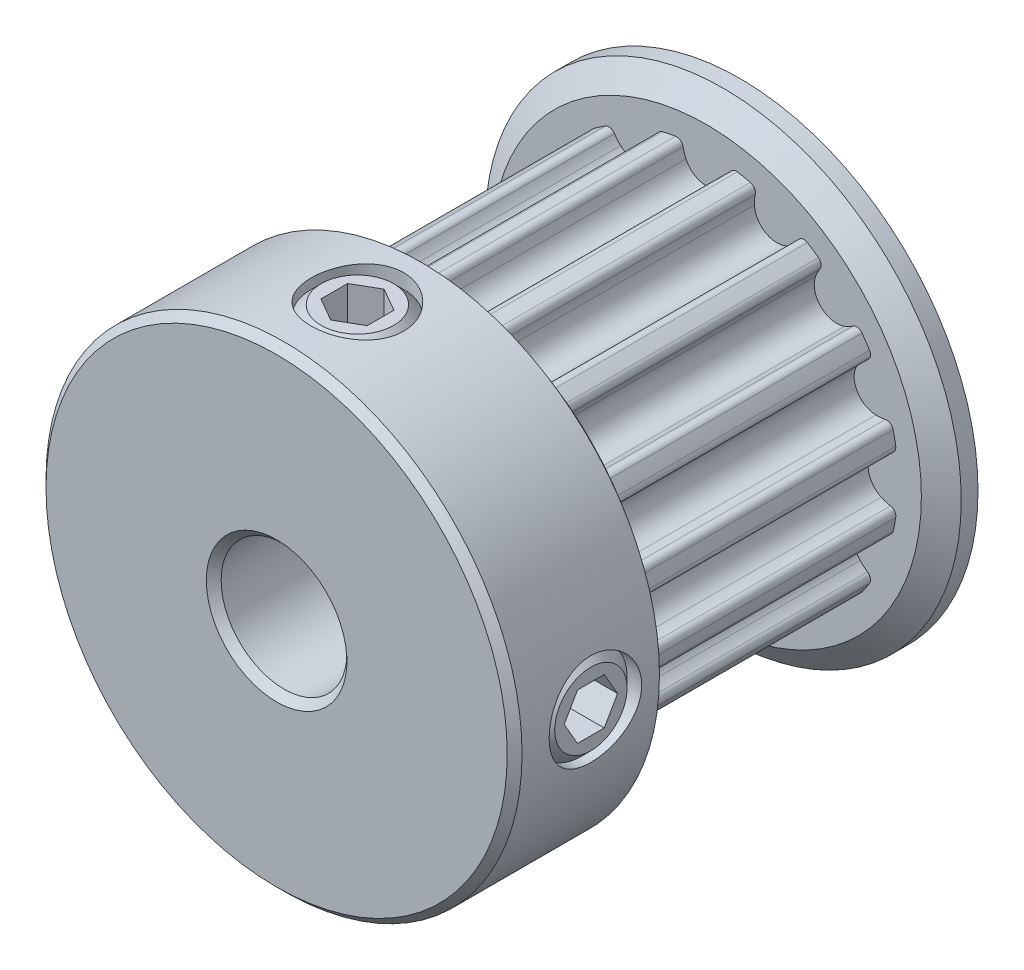
SolidWorks part; units mm, degrees
ref_plane "Front Plane" through (0, 0, 0) normal (0, 0, 1) x (1, 0, 0)
ref_plane "Top Plane" through (0, 0, 0) normal (0, 1, 0) x (1, 0, 0)
ref_plane "Right Plane" through (0, 0, 0) normal (1, 0, 0) x (0, 0, -1)
sketch "Sketch1" plane through (0, 0, 0) normal (0, 0, 1) x (1, 0, 0)
  line L1 (-2.553, 6.1245) -> (2.553, 6.1245) construction
  line L4 (0, 0) -> (0, 6.1245) construction
  line L5 (0, 6.1245) -> (0, 12.0665) construction
  line L6 (0, 7.6455) -> (2.9417, 7.0569) construction
  line L7 (2.9417, 7.0569) -> (3.8741, 6.6682) construction
  line L8 (2.9417, 7.0569) -> (2.553, 6.1245) construction
  line L9 (-2.9417, 7.0569) -> (-2.553, 6.1245) construction
  line L10 (-2.7951, 6.7052) -> (-3.7579, 9.015)
  line L11 (-3.7579, 9.015) -> (3.7579, 9.015)
  line L12 (3.7579, 9.015) -> (2.7951, 6.7052)
  circle A0 centre (0, 0) radius 7.6455 construction
  circle A1 centre (0, 0) radius 9.015 construction
  circle A2 centre (0, 0) radius 7.2645 construction
  arc A3 (-0.7739, 6.6229) -> (0.7739, 6.6229) centre (0, 6.9745) ccw
  arc A4 (-0.7739, 6.6229) -> (-0.8836, 6.9694) centre (0.61, 7.2516) cw
  arc A5 (-2.7951, 6.7052) -> (-1.1695, 7.1697) centre (0, 0) cw
  arc A6 (-0.8836, 6.9694) -> (-1.1695, 7.1697) centre (-1.1292, 6.923) ccw
  arc A7 (2.7951, 6.7052) -> (1.1695, 7.1697) centre (0, 0) ccw
  arc A8 (0.8836, 6.9694) -> (1.1695, 7.1697) centre (1.1292, 6.923) cw
  arc A9 (0.7739, 6.6229) -> (0.8836, 6.9694) centre (-0.61, 7.2516) ccw
  point P6 (0, 20.9083)
  point P11 (0, 7.6455)
  point P13 (0, 9.015)
  point P14 (0, 7.2645)
  dimension "D1" = 8.8419
  dimension "D2" = 4.421
sketch "Sketch2" plane through (0, 0, 0) normal (1, 0, 0) x (0, 0, -1)
  line L0 (-8.775, 2.3812) -> (8.775, 2.3812)
  line L1 (-8.775, 2.3812) -> (-8.775, 9.015)
  line L2 (-3.29, 9.015) -> (-8.775, 9.015)
  line L3 (-3.925, 2.3813) -> (-3.925, 9.015) construction
  line L4 (-3.925, 9.015) -> (-2.655, 9.015) construction
  line L5 (-2.655, 9.015) -> (-2.655, 7.2645) construction
  line L6 (-2.655, 7.2645) -> (7.505, 7.2645)
  line L7 (7.505, 7.2645) -> (7.505, 9.015) construction
  line L8 (7.505, 9.015) -> (8.775, 9.015) construction
  line L9 (8.775, 9.015) -> (8.775, 2.3812)
  line L10 (-8.775, 0) -> (8.775, 0) construction
  line L11 (8.14, 9.015) -> (7.505, 8.1398)
  line L12 (-2.655, 8.1398) -> (-3.29, 9.015)
  line L14 (-2.655, 8.1398) -> (-2.655, 7.2645)
  line L15 (7.505, 7.2645) -> (7.505, 8.1398)
  line L16 (8.14, 9.015) -> (8.775, 9.015)
  arc A0 (-2.655, 8.1398) -> (-3.29, 9.015) centre (-3.5757, 8.1398) ccw construction
  arc A1 (7.505, 8.1398) -> (8.14, 9.015) centre (8.4257, 8.1398) cw construction
  point P12 (-2.655, 8.1398)
  point P14 (-3.29, 9.015)
  point P20 (7.505, 8.1398)
  point P21 (8.14, 9.015)
  point P25 (7.505, 0)
  point P26 (-2.655, 0)
  dimension "OA" = 17.55
  dimension "Bore" = 4.7625
  dimension "Outside Width" = 11.43
  dimension "Inside Width" = 10.16
revolve "Revolve1" add sketch "Sketch2" angle 360 mid plane about L10
sketch "Sketch3" plane through (0, 0, 0) normal (0, 0, 1) x (1, 0, 0)
  line L6 (3.7579, 9.015) -> (-3.7579, 9.015)
  line L7 (2.7951, 6.7052) -> (3.7579, 9.015)
  line L8 (-3.7579, 9.015) -> (-2.7951, 6.7052)
  line L9 (3.7579, 9.015) -> (-3.7579, 9.015)
  line L10 (2.7951, 6.7052) -> (3.7579, 9.015)
  line L11 (-3.7579, 9.015) -> (-2.7951, 6.7052)
  arc A8 (2.7951, 6.7052) -> (1.1695, 7.1697) centre (0, 0) ccw
  arc A9 (1.1695, 7.1697) -> (0.8836, 6.9694) centre (1.1292, 6.923) ccw
  arc A10 (0.7739, 6.6229) -> (0.8836, 6.9694) centre (-0.61, 7.2516) ccw
  arc A11 (-0.7739, 6.6229) -> (0.7739, 6.6229) centre (0, 6.9745) ccw
  arc A12 (-0.8836, 6.9694) -> (-0.7739, 6.6229) centre (0.61, 7.2516) ccw
  arc A13 (-0.8836, 6.9694) -> (-1.1695, 7.1697) centre (-1.1292, 6.923) ccw
  arc A14 (-1.1695, 7.1697) -> (-2.7951, 6.7052) centre (0, 0) ccw
  arc A15 (2.7951, 6.7052) -> (1.1695, 7.1697) centre (0, 0) ccw
  arc A16 (1.1695, 7.1697) -> (0.8836, 6.9694) centre (1.1292, 6.923) ccw
  arc A17 (0.7739, 6.6229) -> (0.8836, 6.9694) centre (-0.61, 7.2516) ccw
  arc A18 (-0.7739, 6.6229) -> (0.7739, 6.6229) centre (0, 6.9745) ccw
  arc A19 (-0.8836, 6.9694) -> (-0.7739, 6.6229) centre (0.61, 7.2516) ccw
  arc A20 (-0.8836, 6.9694) -> (-1.1695, 7.1697) centre (-1.1292, 6.923) ccw
  arc A21 (-1.1695, 7.1697) -> (-2.7951, 6.7052) centre (0, 0) ccw
  dimension "D1" = 0
extrude "Cut-Extrude1" cut sketch "Sketch3" against normal up to vertex (7.505 mm away) from vertex up to point (0, 7.2645, -7.505) starting at point (0, 7.2645, 2.655)
pattern_circular "CirPattern1" count 16 over 360 about axis through (0, 0, 8.775) along (0, 0, 1) of "Cut-Extrude1"
sketch "Sketch4" plane through (0, 0, 0) normal (1, 0, 0) x (0, -1, 0)
  line L0 (0, -2.655) -> (0, -8.775) construction
  line L1 (-2.3812, -8.775) -> (2.3812, -8.775) construction
  line L2 (8.1398, -2.655) -> (-8.1398, -2.655) construction
  circle A0 centre (0, -5.715) radius 1.7526
extrude "Cut-Extrude2" cut sketch "Sketch4" along normal through all
ref_plane "Plane1" through (0, 0, 5.715) normal (0, 0, 1) x (1, 0, 0)
sketch "Sketch5" plane through (0, 0, 5.715) normal (0, 0, 1) x (1, 0, 0)
  line L0 (0, 0) -> (0, 9.015) construction
  line L1 (2.3812, -1.3716) -> (2.3812, 0)
  line L2 (2.7622, -1.7526) -> (8.462, -1.7526)
  line L3 (2.3812, 0) -> (9.015, 0) construction
  line L4 (2.3812, 0) -> (8.843, 0)
  line L5 (8.843, 0) -> (8.843, -1.3716)
  line L6 (2.7622, -1.7526) -> (2.3812, -1.3716)
  line L7 (8.843, -1.3716) -> (8.462, -1.7526)
  circle A0 centre (0, 0) radius 9.015 construction
  circle A1 centre (0, 0) radius 2.3812 construction
  point P2 (2.3812, -1.7526)
  point P11 (8.843, -1.7526)
revolve "Revolve2" add sketch "Sketch5" angle 360 mid plane about L4
sketch "Sketch6" plane through (8.843, 5.3841, 0) normal (-1, 0, 0) x (0, -1, 0)
  line L1 (5.3841, 6.7269) -> (4.5078, 6.2209)
  line L2 (4.5078, 6.2209) -> (4.5078, 5.2091)
  line L3 (4.5078, 5.2091) -> (5.3841, 4.7031)
  line L4 (5.3841, 4.7031) -> (6.2604, 5.2091)
  line L5 (6.2604, 5.2091) -> (6.2604, 6.2209)
  line L6 (6.2604, 6.2209) -> (5.3841, 6.7269)
  circle A0 centre (5.3841, 5.715) radius 0.8763 construction
  dimension "D1" = 1.7526
extrude "Cut-Extrude3" cut sketch "Sketch6" along normal blind 1.3144
pattern_circular "CirPattern3" count 2 over 90 about axis through (0, 0, 8.775) along (0, 0, 1) of "Cut-Extrude2", "Revolve2", "Cut-Extrude3"
chamfer "Chamfer1" distance 0.2807 angle 45 2 edges at (2.3812, 0, 8.775) (9.015, 0, 8.775)
ref_axis "Center Axis 1" through (0, 0, -8.775) along (0, 0, 1)
ref_plane "Contact Plane 1" through (0, 0, 8.775) normal (0, 0, 1) x (1, 0, 0)
ref_plane "Contact Plane 2" through (0, 0, -8.775) normal (0, 0, -1) x (-1, 0, 0)
equation "\"D2@Sketch1\"= \"D1@Sketch1\" / 2"
equation "\"D1@Sketch6\" = \"Set Screw@Sketch4\" / 2"
equation "\"D1@Cut-Extrude3\" = \"D1@Sketch6\"*.75"
